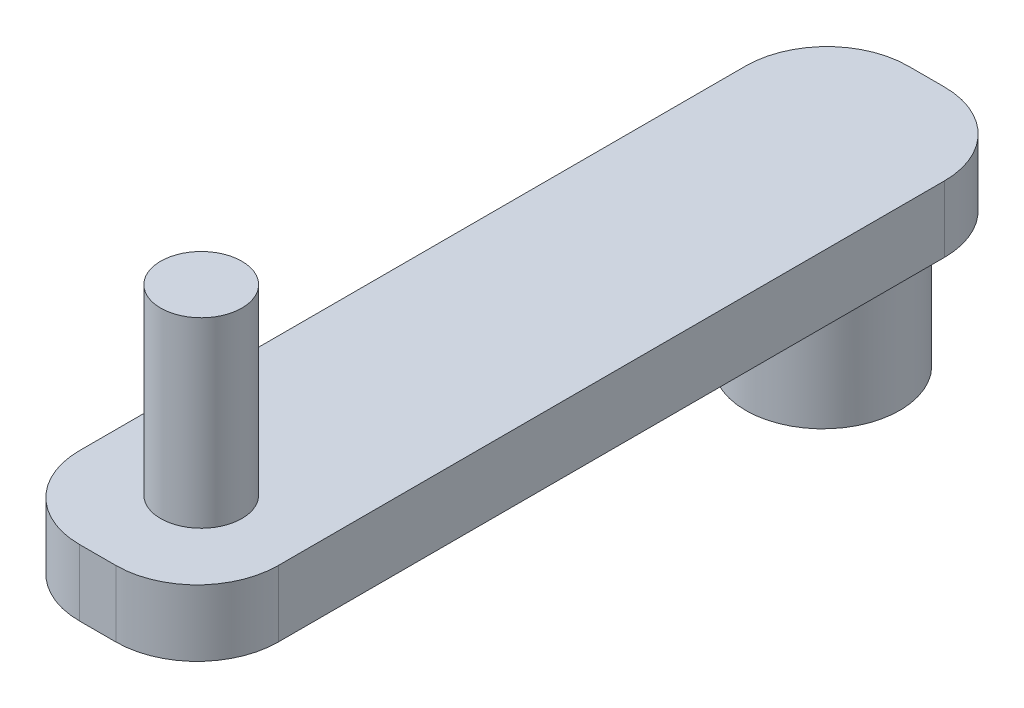
SolidWorks part; units mm, degrees
ref_plane "Front Plane" through (0, 0, 0) normal (0, 0, 1) x (1, 0, 0)
ref_plane "Top Plane" through (0, 0, 0) normal (0, 1, 0) x (1, 0, 0)
ref_plane "Right Plane" through (0, 0, 0) normal (1, 0, 0) x (0, 0, -1)
sketch "Sketch2" plane through (0, 0, 0) normal (0, 1, 0) x (1, 0, 0)
  line L0 (-55, 0) -> (55, 0) construction
  line L1 (-1.1, -25) -> (1.1, -25)
  line L2 (-6, -20.1) -> (-6, 20.1)
  line L3 (-1.1, 25) -> (1.1, 25)
  line L4 (6, -20.1) -> (6, 20.1)
  line L5 (-6, -25) -> (6, 25) construction
  line L6 (-6, 25) -> (6, -25) construction
  circle A0 centre (0, 18.75) radius 4.65
  arc A1 (1.1, -25) -> (6, -20.1) centre (1.1, -20.1) ccw
  arc A2 (-1.1, -25) -> (-6, -20.1) centre (-1.1, -20.1) cw
  arc A3 (-6, 20.1) -> (-1.1, 25) centre (-1.1, 20.1) cw
  arc A4 (6, 20.1) -> (1.1, 25) centre (1.1, 20.1) ccw
  circle A5 centre (0, -18.75) radius 2.45
  point P0 (0, 0)
  dimension "D3" = 9.3
  dimension "D5" = 4.9
  dimension "D4" = 4.9
  dimension "D1" = 50
  dimension "D2" = 12
  dimension "D6" = 37.5
extrude "Boss-Extrude1" add sketch "Sketch2" along normal blind 4 contours L2 A3 L3 A4 L4 A1 L1 A2
extrude "Boss-Extrude2" add sketch "Sketch2<3>" against normal blind 8 contours A0 region at (0, 0, -18.75)
sketch "Sketch2<3>" plane through (0, 0, 0) normal (0, 1, 0) x (1, 0, 0) same geometry as "Sketch2"
extrude "Boss-Extrude3" add sketch "Sketch2<4>" along normal blind 15 contours A5
sketch "Sketch2<4>" plane through (0, 0, 0) normal (0, 1, 0) x (1, 0, 0) same geometry as "Sketch2"
